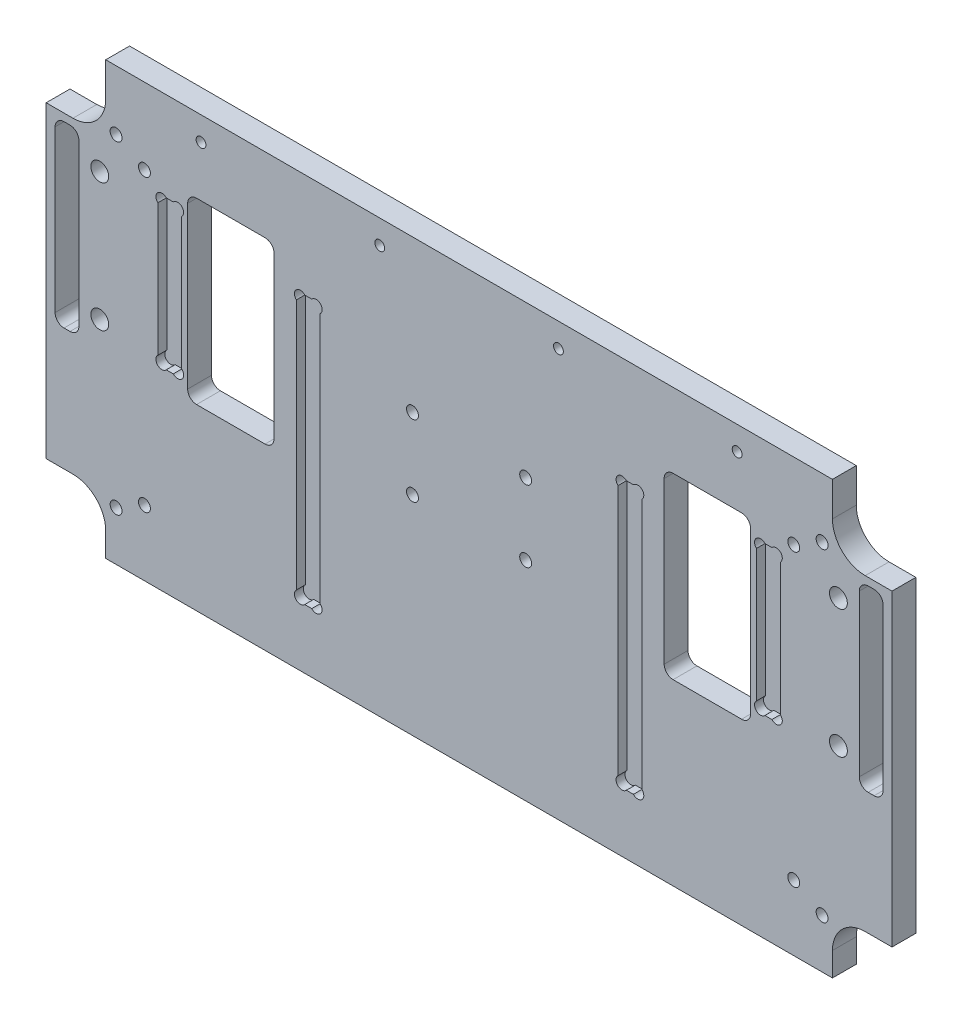
SolidWorks part; units mm, degrees
ref_plane "Front" through (0, 0, 0) normal (0, 0, 1) x (1, 0, 0)
ref_plane "Top" through (0, 0, 0) normal (0, 1, 0) x (1, 0, 0)
ref_plane "Right" through (0, 0, 0) normal (1, 0, 0) x (0, 0, -1)
sketch "Esquisse1" plane through (0, 0, 0) normal (0, 0, 1) x (1, 0, 0)
  line L1 (0, 0) -> (284, 0)
  line L2 (0, 0) -> (0, 145)
  line L3 (0, 145) -> (284, 145)
  line L4 (284, 0) -> (284, 145)
  dimension "D1" = 284
  dimension "D2" = 145
extrude "Boss.-Extru.1" add sketch "Esquisse1" along normal blind 8
sketch "Esquisse2" plane through (0, 0, 8) normal (0, 0, 1) x (1, 0, 0)
  line L0 (142, 145) -> (142, 0) construction
  line L1 (47.5, 60) -> (76.5, 60)
  line L2 (47.5, 60) -> (47.5, 120)
  line L3 (47.5, 120) -> (76.5, 120)
  line L4 (76.5, 60) -> (76.5, 120)
  line L5 (284, 145) -> (0, 145) construction
  line L6 (0, 0) -> (284, 0) construction
  line L7 (76.5, 90) -> (142, 90) construction
  line L8 (62, 60) -> (62, 120) construction
  line L9 (47.5, 90) -> (11, 90) construction
  line L10 (7, 60) -> (7, 120) construction
  line L11 (3, 60) -> (11, 60)
  line L12 (3, 60) -> (3, 120)
  line L13 (3, 120) -> (11, 120)
  line L14 (11, 60) -> (11, 120)
  line L15 (277, 60) -> (277, 120) construction
  line L16 (236.5, 90) -> (273, 90) construction
  line L17 (222, 60) -> (222, 120) construction
  line L18 (273, 60) -> (273, 120)
  line L19 (281, 120) -> (273, 120)
  line L20 (281, 60) -> (281, 120)
  line L21 (281, 60) -> (273, 60)
  line L22 (207.5, 60) -> (207.5, 120)
  line L23 (236.5, 120) -> (207.5, 120)
  line L24 (236.5, 60) -> (236.5, 120)
  line L25 (236.5, 60) -> (207.5, 60)
  dimension "D1" = 55
  dimension "D2" = 60
  dimension "D3" = 29
  dimension "D4" = 160
  dimension "D5" = 8
  dimension "D6" = 60
  dimension "D7" = 270
extrude "Enlèv. mat.-Extru.1" cut sketch "Esquisse2" against normal through all
sketch "Esquisse3" plane through (0, 0, 8) normal (0, 0, 1) x (1, 0, 0)
  line L0 (0, 137) -> (284, 137) construction
  line L1 (0, 145) -> (0, 0) construction
  line L2 (284, 0) -> (284, 145) construction
  line L3 (112, 137) -> (112, 180.3897) construction
  line L5 (172, 137) -> (172, 180.3897) construction
  line L6 (172, 180.3897) -> (112, 180.3897) construction
  line L7 (142, 180.3897) -> (142, 145) construction
  line L8 (284, 145) -> (0, 145) construction
  circle A0 centre (112, 137) radius 1.65
  circle A1 centre (172, 137) radius 1.65
  circle A2 centre (232, 137) radius 1.65
  circle A4 centre (52, 137) radius 1.65
  point P6 (112.0697, 135)
  dimension "D1" = 3.3
  dimension "D2" = 4
  dimension "D3" = 8
  dimension "D4" = 60
extrude "Enlèv. mat.-Extru.2" cut sketch "Esquisse3" against normal up to vertex (8 mm away) up to point (284, 145, 0)
sketch "Esquisse4" plane through (0, 0, 8) normal (0, 0, 1) x (1, 0, 0)
  line L0 (142, 0) -> (142, 145) construction
  line L1 (84, 110) -> (92, 110)
  line L2 (84, 110) -> (84, 20)
  line L3 (84, 20) -> (92, 20)
  line L4 (92, 110) -> (92, 20)
  line L5 (0, 0) -> (284, 0) construction
  line L6 (284, 145) -> (0, 145) construction
  line L8 (76.5, 60) -> (76.5, 120) construction
  line L9 (192, 110) -> (192, 20)
  line L10 (200, 20) -> (192, 20)
  line L11 (200, 110) -> (200, 20)
  line L12 (200, 110) -> (192, 110)
  line L13 (47.5, 120) -> (47.5, 60) construction
  line L14 (37.5, 115) -> (45.5, 115)
  line L15 (37.5, 115) -> (37.5, 65)
  line L16 (37.5, 65) -> (45.5, 65)
  line L17 (45.5, 115) -> (45.5, 65)
  line L18 (45.5, 90) -> (47.5, 90) construction
  line L19 (238.5, 90) -> (236.5, 90) construction
  line L20 (238.5, 115) -> (238.5, 65)
  line L21 (246.5, 65) -> (238.5, 65)
  line L22 (246.5, 115) -> (246.5, 65)
  line L23 (246.5, 115) -> (238.5, 115)
  line L24 (47.5, 60) -> (76.5, 60) construction
  dimension "D1" = 40
  dimension "D2" = 90
  dimension "D3" = 8
  dimension "D4" = 7.5
  dimension "D5" = 8
  dimension "D6" = 2
  dimension "D7" = 50
extrude "Enlèv. mat.-Extru.3" cut sketch "Esquisse4" against normal blind 3
sketch "Esquisse5" plane through (0, 0, 8) normal (0, 0, 1) x (1, 0, 0)
  line L0 (142, 0) -> (142, 124.0722) construction
  line L2 (142, 82) -> (121.1311, 82) construction
  line L3 (0, 145) -> (0, 0) construction
  circle A0 centre (123, 94) radius 2
  circle A1 centre (123, 70) radius 2
  circle A2 centre (161, 70) radius 2
  circle A3 centre (161, 94) radius 2
  circle A5 centre (112, 137) radius 1.65 construction
  dimension "D1" = 38
  dimension "D2" = 4
  dimension "D3" = 24
  dimension "D4" = 55
  dimension "D5" = 142
extrude "Enlèv. mat.-Extru.4" cut sketch "Esquisse5" against normal through all
sketch "Esquisse6" plane through (0, 0, 8) normal (0, 0, 1) x (1, 0, 0)
  line L0 (142, 0) -> (142, 119.0936) construction
  line L1 (0, 0) -> (284, 0) construction
  line L2 (11, 90) -> (29.8915, 90) construction
  line L4 (11, 60) -> (11, 120) construction
  line L5 (273, 90) -> (254.1085, 90) construction
  circle A0 centre (18, 111.5) radius 3
  circle A1 centre (18, 68.5) radius 3
  circle A2 centre (266, 68.5) radius 3
  circle A3 centre (266, 111.5) radius 3
  dimension "D3" = 6
  dimension "D1" = 21.5
  dimension "D2" = 7
extrude "Enlèv. mat.-Extru.5" cut sketch "Esquisse6" against normal through all
sketch "Esquisse8" plane through (0, 0, 8) normal (0, 0, 1) x (1, 0, 0)
  line L0 (142, 145) -> (142, 109.7669) construction
  line L1 (0, 145) -> (20, 145)
  line L2 (0, 145) -> (0, 122.5)
  line L3 (0, 122.5) -> (20, 122.5)
  line L4 (20, 145) -> (20, 122.5)
  line L5 (284, 145) -> (0, 145) construction
  line L6 (264, 145) -> (264, 122.5)
  line L7 (284, 122.5) -> (264, 122.5)
  line L8 (284, 145) -> (284, 122.5)
  line L9 (284, 145) -> (264, 145)
  line L10 (264, 0) -> (264, 19)
  line L11 (0, 0) -> (20, 0)
  line L12 (0, 0) -> (0, 19)
  line L13 (0, 19) -> (20, 19)
  line L14 (20, 0) -> (20, 19)
  line L15 (284, 19) -> (264, 19)
  line L16 (284, 0) -> (284, 19)
  line L17 (284, 0) -> (264, 0)
  dimension "D1" = 22.5
  dimension "D2" = 20
  dimension "D3" = 19
extrude "Enlèv. mat.-Extru.7" cut sketch "Esquisse8" against normal through all
fillet "Congé1" radius 11 4 edges at (20, 122.5, 4) (264, 122.5, 4) (264, 19, 4) (20, 19, 4)
sketch "Esquisse7" plane through (0, 0, 8) normal (0, 0, 1) x (1, 0, 0)
  line L0 (142, 145) -> (142, 7.3256) construction
  line L1 (264, 145) -> (20, 145) construction
  line L2 (23.4737, 125) -> (33, 119.5) construction
  line L4 (260.5263, 125) -> (251, 119.5) construction
  line L5 (33, 119.5) -> (33, 22) construction
  line L6 (33, 70.75) -> (100.6533, 70.75) construction
  line L7 (23.4737, 16.5) -> (33, 22) construction
  line L8 (20, 0) -> (264, 0) construction
  line L9 (260.5263, 16.5) -> (251, 22) construction
  circle A0 centre (33, 119.5) radius 2
  circle A1 centre (23.4737, 125) radius 2
  circle A2 centre (260.5263, 125) radius 2
  circle A3 centre (251, 119.5) radius 2
  circle A4 centre (18, 111.5) radius 3 construction
  circle A5 centre (23.4737, 16.5) radius 2
  circle A6 centre (33, 22) radius 2
  circle A7 centre (251, 22) radius 2
  circle A8 centre (260.5263, 16.5) radius 2
  dimension "D1" = 4
  dimension "D2" = 11
  dimension "D3" = 109
  dimension "D4" = 30
  dimension "D5" = 8
  dimension "D6" = 22
extrude "Enlèv. mat.-Extru.6" cut sketch "Esquisse7" against normal through all
fillet "Congé2" radius 3 16 edges at (281, 60, 4) (273, 60, 4) (281, 120, 4) (273, 120, 4) (236.5, 120, 4) (207.5, 120, 4) (236.5, 60, 4) (207.5, 60, 4) (76.5, 60, 4) (47.5, 60, 4) (76.5, 120, 4) (47.5, 120, 4) (11, 120, 4) (3, 120, 4) (3, 60, 4) (11, 60, 4)
sketch "Esquisse9" plane through (0, 0, 8) normal (0, 0, 1) x (1, 0, 0)
  line L0 (37.5, 115) -> (38.8435, 113.6565) construction
  line L1 (45.5, 115) -> (37.5, 115) construction
  line L2 (41.5, 115) -> (41.5, 118.2808) construction
  line L3 (45.5, 115) -> (37.5, 115) construction
  line L4 (45.5, 115) -> (44.1565, 113.6565) construction
  line L5 (45.5, 90) -> (42.8729, 90) construction
  line L6 (45.5, 65) -> (45.5, 115) construction
  line L7 (45.5, 65) -> (44.1565, 66.3435) construction
  line L8 (37.5, 65) -> (38.8435, 66.3435) construction
  line L9 (45.5, 90) -> (238.5, 90) construction
  line L10 (238.5, 115) -> (238.5, 65) construction
  line L11 (142, 90) -> (142, 121.5895) construction
  line L12 (246.5, 65) -> (245.1565, 66.3435) construction
  line L13 (238.5, 65) -> (239.8435, 66.3435) construction
  line L14 (238.5, 90) -> (241.1271, 90) construction
  line L15 (238.5, 115) -> (239.8435, 113.6565) construction
  line L16 (242.5, 115) -> (242.5, 118.2808) construction
  line L17 (246.5, 115) -> (245.1565, 113.6565) construction
  line L18 (84, 110) -> (85.3435, 108.6565) construction
  line L19 (92, 110) -> (84, 110) construction
  line L20 (88, 110) -> (88, 112.2434) construction
  line L21 (92, 110) -> (84, 110) construction
  line L22 (92, 110) -> (90.6565, 108.6565) construction
  line L23 (84, 65) -> (89.3356, 65) construction
  line L24 (84, 110) -> (84, 20) construction
  line L25 (92, 20) -> (90.6565, 21.3435) construction
  line L26 (88, 20) -> (88, 17.7566) construction
  line L27 (84, 20) -> (85.3435, 21.3435) construction
  line L28 (200, 20) -> (198.6565, 21.3435) construction
  line L29 (196, 20) -> (196, 17.7566) construction
  line L30 (192, 20) -> (193.3435, 21.3435) construction
  line L31 (200, 65) -> (194.6644, 65) construction
  line L32 (192, 110) -> (193.3435, 108.6565) construction
  line L33 (196, 110) -> (196, 112.2434) construction
  line L34 (200, 110) -> (198.6565, 108.6565) construction
  circle A0 centre (38.8435, 113.6565) radius 2
  circle A1 centre (44.1565, 113.6565) radius 2
  circle A2 centre (44.1565, 66.3435) radius 2
  circle A3 centre (38.8435, 66.3435) radius 2
  circle A4 centre (245.1565, 66.3435) radius 2
  circle A5 centre (239.8435, 66.3435) radius 2
  circle A6 centre (239.8435, 113.6565) radius 2
  circle A7 centre (245.1565, 113.6565) radius 2
  circle A8 centre (85.3435, 108.6565) radius 2
  circle A9 centre (90.6565, 108.6565) radius 2
  circle A10 centre (90.6565, 21.3435) radius 2
  circle A11 centre (85.3435, 21.3435) radius 2
  circle A12 centre (198.6565, 21.3435) radius 2
  circle A13 centre (193.3435, 21.3435) radius 2
  circle A14 centre (193.3435, 108.6565) radius 2
  circle A15 centre (198.6565, 108.6565) radius 2
  dimension "D1" = 4
  dimension "D6" = 4
  dimension "D2" = 45
  dimension "D3" = 1.9
  dimension "D4" = 45
  dimension "D5" = 1.9
extrude "Enlèv. mat.-Extru.8" cut sketch "Esquisse9" against normal up to vertex (3 mm away) up to point (37.5, 65, 5)
